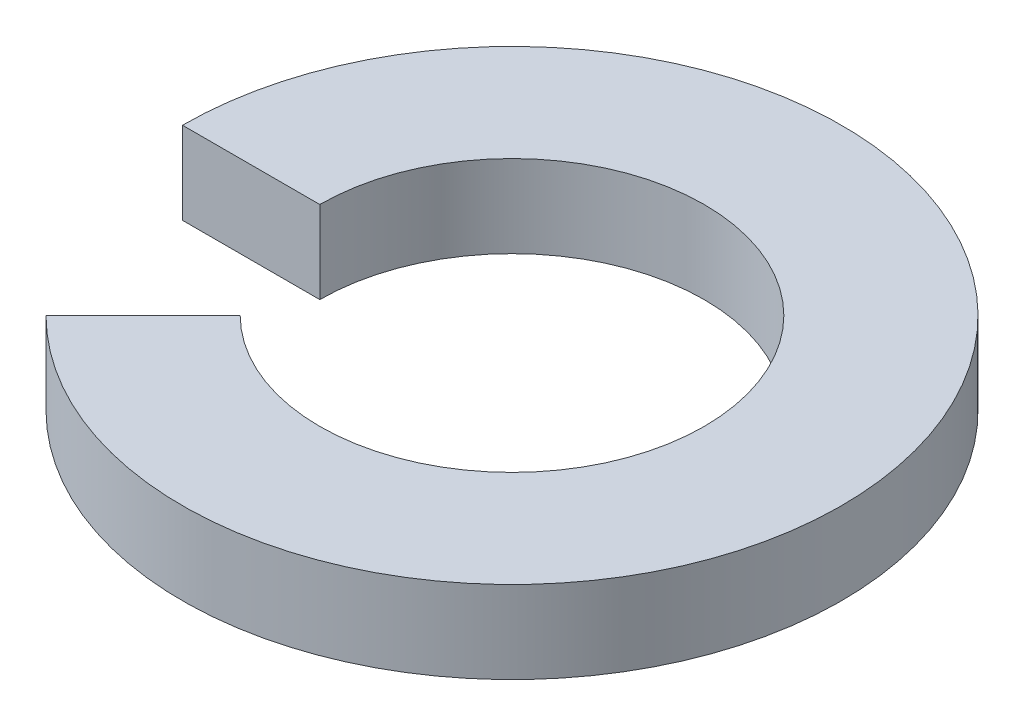
SolidWorks part; units mm, degrees
ref_plane "Front Plane" through (0, 0, 0) normal (0, 0, 1) x (1, 0, 0)
ref_plane "Top Plane" through (0, 0, 0) normal (0, 1, 0) x (1, 0, 0)
ref_plane "Right Plane" through (0, 0, 0) normal (1, 0, 0) x (0, 0, -1)
sketch "Sketch1" plane through (0, 0, 0) normal (0, 1, 0) x (1, 0, 0)
  line L0 (0, 0) -> (-6, 0)
  line L1 (0, 0) -> (-4.2426, -4.2426)
  arc A0 (-2.4749, -2.4749) -> (-3.5, 0) centre (0, 0) ccw
  arc A1 (-4.2426, -4.2426) -> (-6, 0) centre (0, 0) ccw
  dimension "D1" = 7
  dimension "D2" = 12
  dimension "D3" = 45
extrude "Boss-Extrude1" add sketch "Sketch1" along normal blind 1.5 contours L1 A1 L0 A0 region at (-4.75, 0, -0.1697)
